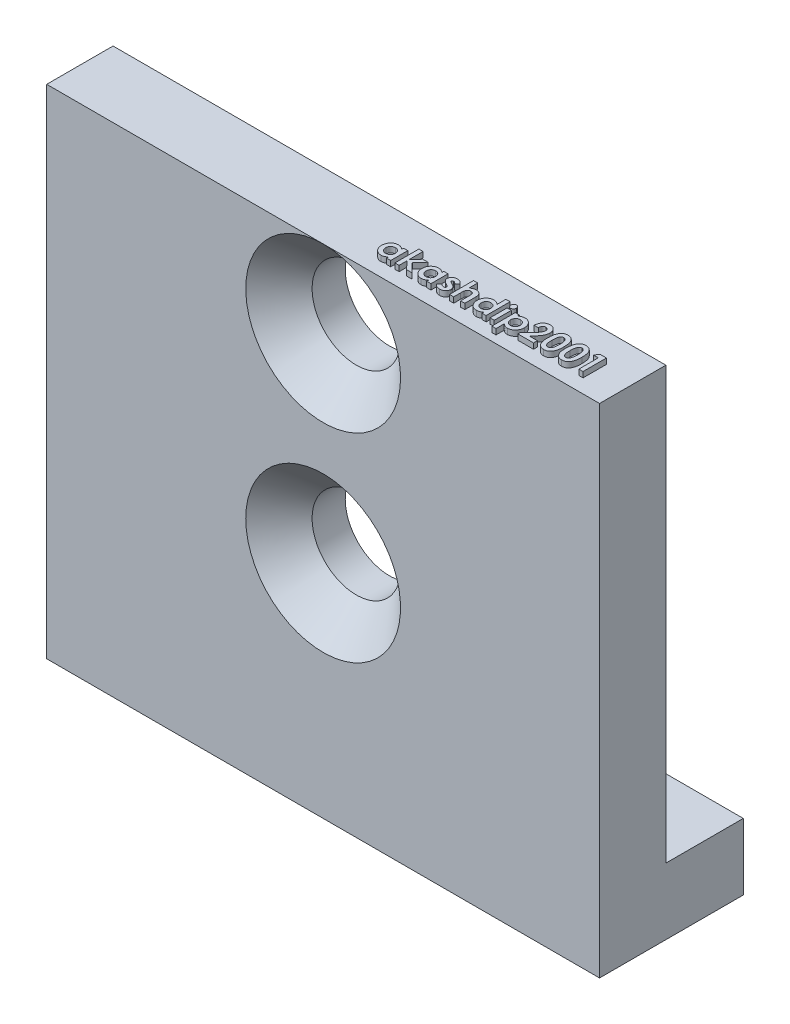
SolidWorks part; units mm, degrees
ref_plane "Front Plane" through (0, 0, 0) normal (0, 0, 1) x (1, 0, 0)
ref_plane "Top Plane" through (0, 0, 0) normal (0, 1, 0) x (1, 0, 0)
ref_plane "Right Plane" through (0, 0, 0) normal (1, 0, 0) x (0, 0, -1)
sketch "Sketch1" plane through (0, 0, 0) normal (0, 0, 1) x (1, 0, 0)
  line L0 (0, 0) -> (0, 20790.1296) construction
  line L1 (0, 0) -> (20790.1296, 0) construction
  line L3 (-25, -22.5) -> (25, -22.5)
  line L4 (-25, -22.5) -> (-25, 22.5)
  line L5 (-25, 22.5) -> (25, 22.5)
  line L6 (25, -22.5) -> (25, 22.5)
  line L7 (-25, -22.5) -> (25, 22.5) construction
  line L8 (-25, 22.5) -> (25, -22.5) construction
  point P5 (0, 0)
  dimension "D1" = 50
  dimension "D2" = 45
extrude "Boss-Extrude1" add sketch "Sketch1" along normal mid plane 6
sketch "Sketch2" plane through (0, 0, -3) normal (0, 0, -1) x (-1, 0, 0)
  line L0 (25, 22.5) -> (25, -22.5) construction
  line L1 (-25, -22.5) -> (25, -22.5)
  line L2 (-25, -22.5) -> (-25, -16.5)
  line L3 (-25, -16.5) -> (25, -16.5)
  line L4 (25, -22.5) -> (25, -16.5)
  dimension "D1" = 6
extrude "Boss-Extrude2" add sketch "Sketch2" along normal blind 7
hole_wizard "Ø8.0mm Dowel Hole1" positions "Sketch4" profile "Sketch5" hole size "Ø8.0" standard "ISO" end condition through all
sketch "Sketch4" plane through (0, 0, 3) normal (0, 0, 1) x (1, 0, 0)
  line L0 (25, 22.5) -> (-25, 22.5) construction
  point P0 (0, 15.5)
  point P2 (0, -2.5)
  dimension "D1" = 7
  dimension "D2" = 18
  dimension "D3" = 25
sketch "Sketch5" plane through (0, 15.5, 3) normal (1, 0, 0) x (0, -1, 0)
  line L0 (0, 0) -> (0, 13)
  line L1 (0, 13) -> (4, 13)
  line L2 (4, 13) -> (4, 0)
  line L5 (4, 0) -> (0, 0)
  line L11 (0, -6.35) -> (0, 107.95) construction
  dimension "Thru Hole Dia." = 8
  dimension "Thru Hole Depth" = 13
chamfer "Chamfer1" distance 3 angle 45 2 edges at (4, -2.5, 3) (4, 15.5, 3)
sketch "Sketch6" plane through (0, 22.5, 0) normal (0, 1, 0) x (1, 0, 0)
  line L0 (3.1174, -1.743) -> (22.4456, -1.743) construction
  text T0 "<b>akashdip2001</b>" font "Century Gothic" height in points 8
extrude "Boss-Extrude3" add sketch "Sketch6" along normal blind 0.5
